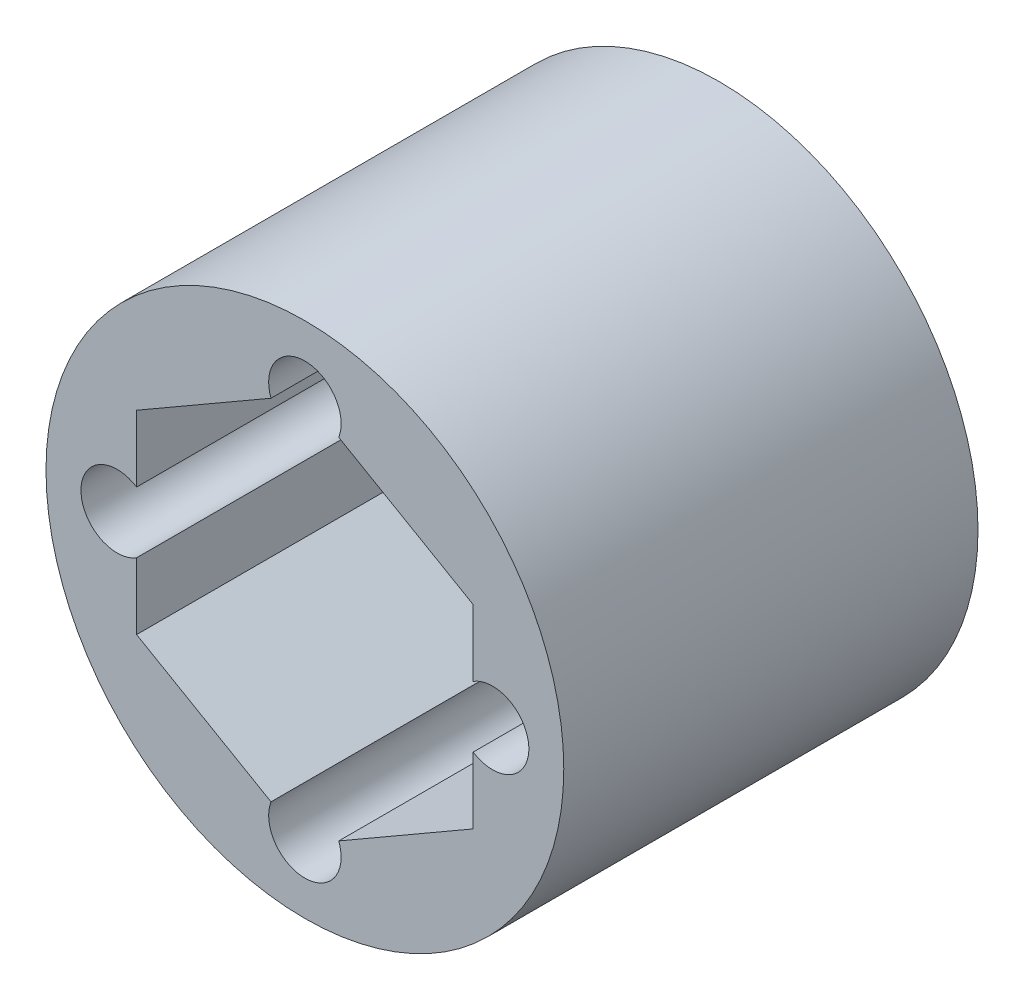
SolidWorks part; units mm, degrees
ref_plane "Front Plane" through (0, 0, 0) normal (0, 0, 1) x (1, 0, 0)
ref_plane "Top Plane" through (0, 0, 0) normal (0, 1, 0) x (1, 0, 0)
ref_plane "Right Plane" through (0, 0, 0) normal (1, 0, 0) x (0, 0, -1)
sketch "Sketch1" plane through (0, 0, 0) normal (0, 0, 1) x (1, 0, 0)
  line L0 (0, 0) -> (0, 12.391) construction
  circle A0 centre (0, 0) radius 10
  circle A1 centre (0, 7.25) radius 1.4
  circle A2 centre (0, 0) radius 4.25
  circle A3 centre (7.25, 0) radius 1.4
  circle A4 centre (0, -7.25) radius 1.4
  circle A5 centre (-7.25, 0) radius 1.4
  dimension "D1" = 20
  dimension "D2" = 2.8
  dimension "D4" = 8.5
  dimension "D3" = 7.25
  dimension "D5" = 4
extrude "Boss-Extrude1" add sketch "Sketch1" along normal blind 16
sketch "Sketch2" plane through (0, 0, 16) normal (0, 0, 1) x (1, 0, 0)
  line L1 (0, 7.5056) -> (-6.5, 3.7528)
  line L2 (-6.5, 3.7528) -> (-6.5, -3.7528)
  line L3 (-6.5, -3.7528) -> (0, -7.5056)
  line L4 (0, -7.5056) -> (6.5, -3.7528)
  line L5 (6.5, -3.7528) -> (6.5, 3.7528)
  line L6 (6.5, 3.7528) -> (0, 7.5056)
  circle A0 centre (0, 0) radius 6.5 construction
  dimension "D1" = 13
extrude "Cut-Extrude1" cut sketch "Sketch2" against normal blind 14
